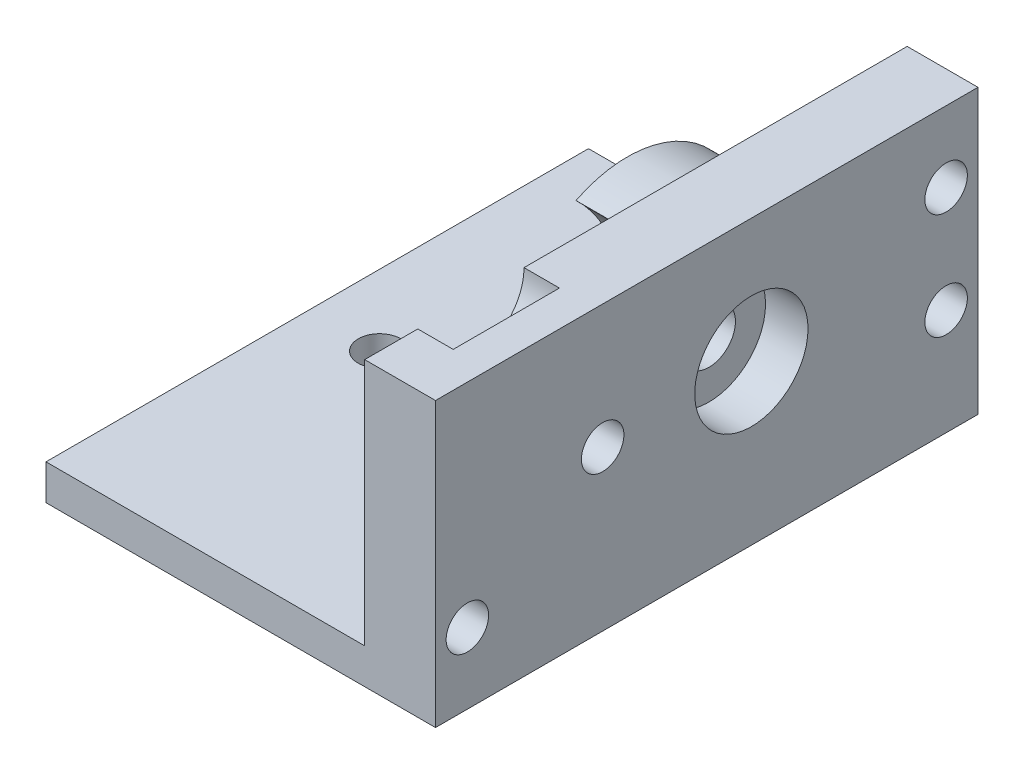
SolidWorks part; units mm, degrees
ref_plane "前视基准面" through (0, 0, 0) normal (0, 0, 1) x (1, 0, 0)
ref_plane "上视基准面" through (0, 0, 0) normal (0, 1, 0) x (1, 0, 0)
ref_plane "右视基准面" through (0, 0, 0) normal (1, 0, 0) x (0, 0, -1)
other "Configuration Table"
sketch "草图1" plane through (0, 0, 0) normal (1, 0, 0) x (0, 0, -1)
  line L9 (0, 0) -> (-15.52, 0)
  line L10 (0, 0) -> (0, -7)
  line L11 (0, -7) -> (-15.52, -7)
  line L12 (-15.52, 0) -> (-15.52, -7)
  circle A5 centre (-6.5, -3.5) radius 3.25
  circle A6 centre (-10.7, -3.5) radius 4
  circle A7 centre (-12.4205, 0) radius 1.5
  circle A8 centre (-12.4205, 0) radius 3.1
  circle A9 centre (-10.7, -3.5) radius 0.6
  circle A10 centre (-6.5, -3.5) radius 0.75
  circle A11 centre (-6.5, -3.5) radius 1.6
  point P12 (0, -3.5)
  dimension "D1" = 4.2
  dimension "D4" = 6.5
  dimension "D5" = 8
  dimension "D9" = 3
  dimension "D10" = 6.2
  dimension "D11" = 1.2
  dimension "D12" = 1.5
  dimension "D13" = 3.2
  dimension "D2" = 3.9
  dimension "D3" = 3.5
  dimension "D6" = 7
  dimension "D7" = 15.52
  dimension "D8" = 6.5
extrude "凸台-拉伸1" add sketch "草图1" along normal blind 2 contours L10 L11 L12 L9
extrude "凸台-拉伸3" add sketch "草图1<6>" against normal blind 1.5 contours A10 A6 A5 region at (0, -0.8039, 4.8332)
sketch "草图1<6>" plane through (0, 0, 0) normal (1, 0, 0) x (0, 0, -1) same geometry as "草图1"
extrude "切除-拉伸1" cut sketch "草图1<8>" along normal blind 1 contours A7
sketch "草图1<8>" plane through (0, 0, 0) normal (1, 0, 0) x (0, 0, -1) same geometry as "草图1"
sketch "草图2" plane through (2, 0, 0) normal (1, 0, 0) x (0, 0, -1)
  line L0 (0, -7) -> (-15.52, -7) construction
  line L1 (-15.52, 0) -> (-15.52, -7) construction
  line L2 (0, 0) -> (-15.52, 0) construction
  line L3 (0, 0) -> (0, -7) construction
  circle A0 centre (-1, -2) radius 0.6
  circle A1 centre (-1, -5) radius 0.6
  circle A2 centre (-14.52, -6) radius 0.6
  dimension "D1" = 1.2
  dimension "D2" = 1
  dimension "D3" = 1
  dimension "D4" = 2
  dimension "D5" = 2
  dimension "D6" = 1
  dimension "D7" = 1
extrude "切除-拉伸2" cut sketch "草图2" against normal through all contours A2 | A1 | A0
extrude "切除-拉伸4" cut sketch "草图1<9>" against normal through all both and the other way through all contours A9 | A10
sketch "草图1<9>" plane through (0, 0, 0) normal (1, 0, 0) x (0, 0, -1) same geometry as "草图1"
sketch "草图3" plane through (0, -7, 0) normal (0, -1, 0) x (1, 0, 0)
  line L0 (2, 15.52) -> (0, 15.52) construction
  line L1 (2, 15.52) -> (-9, 15.52)
  line L2 (2, 15.52) -> (2, 0)
  line L3 (2, 0) -> (-9, 0)
  line L4 (-9, 15.52) -> (-9, 0)
  line L5 (2, 0) -> (0, 0) construction
  circle A0 centre (-7, 8) radius 0.6
  dimension "D2" = 1.2
  dimension "D1" = 11
extrude "凸台-拉伸4" add sketch "草图3" along normal blind 1
extrude "切除-拉伸6" cut sketch "草图1<10>" against normal blind 1.2 from surface contours A11 starting at face at (2, -3.5, 10.1)
sketch "草图1<10>" plane through (0, 0, 0) normal (1, 0, 0) x (0, 0, -1) same geometry as "草图1"
sketch "草图4" plane through (2, 0, 0) normal (1, 0, 0) x (0, 0, -1)
  line L0 (0, 0) -> (-15.52, 0) construction
  line L1 (-15.42, 0) -> (-0.1, 0)
  line L2 (-15.42, 0) -> (-15.42, -8)
  line L3 (-15.42, -8) -> (-0.1, -8)
  line L4 (-0.1, 0) -> (-0.1, -8)
  line L5 (0, -8) -> (-15.52, -8) construction
  line L6 (-15.52, 0) -> (-15.52, -8) construction
  line L7 (0, 0) -> (0, -8) construction
  dimension "D1" = 0.1
  dimension "D2" = 0.1
extrude "切除-拉伸7" cut sketch "草图4" against normal through all flip side to cut contours L2 L3 L4 L1
